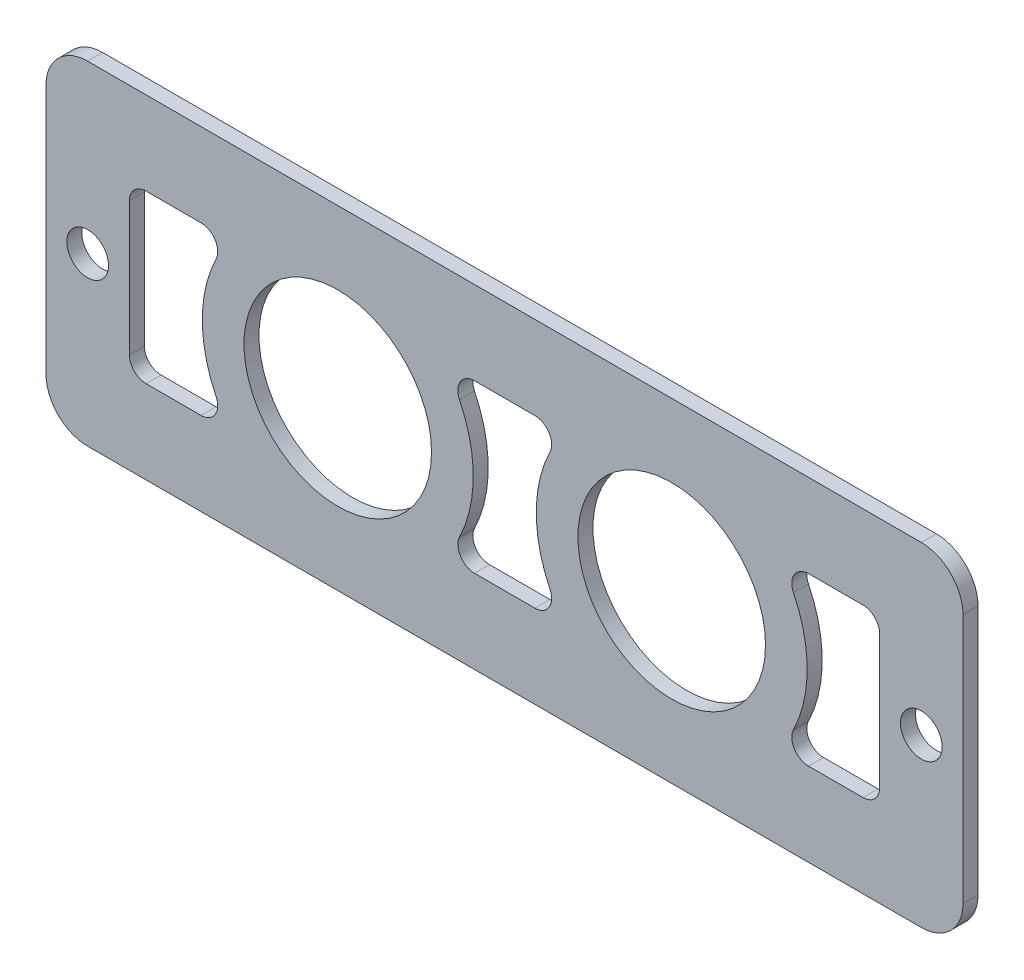
SolidWorks part; units mm, degrees
material "6061-T6 (SS)"
ref_plane "Front Plane" through (0, 0, 0) normal (0, 0, 1) x (1, 0, 0)
ref_plane "Top Plane" through (0, 0, 0) normal (0, 1, 0) x (1, 0, 0)
ref_plane "Right Plane" through (0, 0, 0) normal (1, 0, 0) x (0, 0, -1)
sketch "Sketch1" plane through (0, 0, 0) normal (0, 0, 1) x (1, 0, 0)
  line L0 (-63.5, 0) -> (63.5, 0) construction
  line L1 (-69.85, 25.4) -> (69.85, 25.4)
  line L2 (-69.85, 25.4) -> (-69.85, -25.4)
  line L3 (-69.85, -25.4) -> (69.85, -25.4)
  line L4 (69.85, 25.4) -> (69.85, -25.4)
  line L5 (-69.85, 25.4) -> (69.85, -25.4) construction
  line L6 (-69.85, -25.4) -> (69.85, 25.4) construction
  circle A0 centre (-63.5, 0) radius 3.175
  circle A1 centre (63.5, 0) radius 3.175
  circle A2 centre (-25.4, 0) radius 26.67 construction
  circle A3 centre (25.4762, 0) radius 26.67 construction
  circle A4 centre (-25.4, 0) radius 14.2875
  circle A5 centre (25.4762, 0) radius 14.2875
  point P0 (0, 0)
  dimension "D1" = 6.35
  dimension "D4" = 50.8762
  dimension "D7" = 28.575
  dimension "D2" = 127
  dimension "D3" = 38.1
  dimension "D5" = 139.7
  dimension "D6" = 50.8
extrude "Boss-Extrude1" add sketch "Sketch1" along normal mid plane 2.286
fillet "Fillet1" radius 6.35 4 edges at (69.85, -25.4, 0) (-69.85, -25.4, 0) (-69.85, 25.4, 0) (69.85, 25.4, 0)
sketch "Sketch2" plane through (0, 0, 1.143) normal (0, 0, 1) x (1, 0, 0)
  line L8 (-57.15, -12.7) -> (57.15, -12.7)
  line L9 (57.15, -12.7) -> (57.15, 12.7)
  line L10 (57.15, 12.7) -> (-57.15, 12.7)
  line L11 (-57.15, 12.7) -> (-57.15, -12.7)
  line L12 (-57.15, -12.7) -> (57.15, -12.7)
  line L13 (57.15, -12.7) -> (57.15, 12.7)
  line L14 (57.15, 12.7) -> (-57.15, 12.7)
  line L15 (-57.15, 12.7) -> (-57.15, -12.7)
  circle A9 centre (-25.4, 0) radius 20.6375
  circle A10 centre (-25.4, 0) radius 20.6375
  circle A12 centre (25.4762, 0) radius 20.6375
  circle A13 centre (25.4762, 0) radius 20.6375
  dimension "D1" = 12.7
  dimension "D2" = 6.35
  dimension "D3" = 6.35
extrude "Cut-Extrude1" cut sketch "Sketch2" against normal blind 2.54 contours A10 L14 L15 L12 | A13 L14 A10 L12 | A13 L12 L13 L14 region at (-50.8339, 0, 1.143) region at (0.0381, 0, 1.143) region at (50.8716, 0, 1.143)
fillet "Fillet2" radius 2.54 12 edges at (41.7432, 12.7, 0) (57.15, 12.7, 0) (57.15, -12.7, 0) (-41.667, -12.7, 0) (-57.15, -12.7, 0) (-57.15, 12.7, 0) (-41.667, 12.7, 0) (9.2092, -12.7, 0) (-9.133, 12.7, 0) (9.2092, 12.7, 0) (41.7432, -12.7, 0) (-9.133, -12.7, 0)
